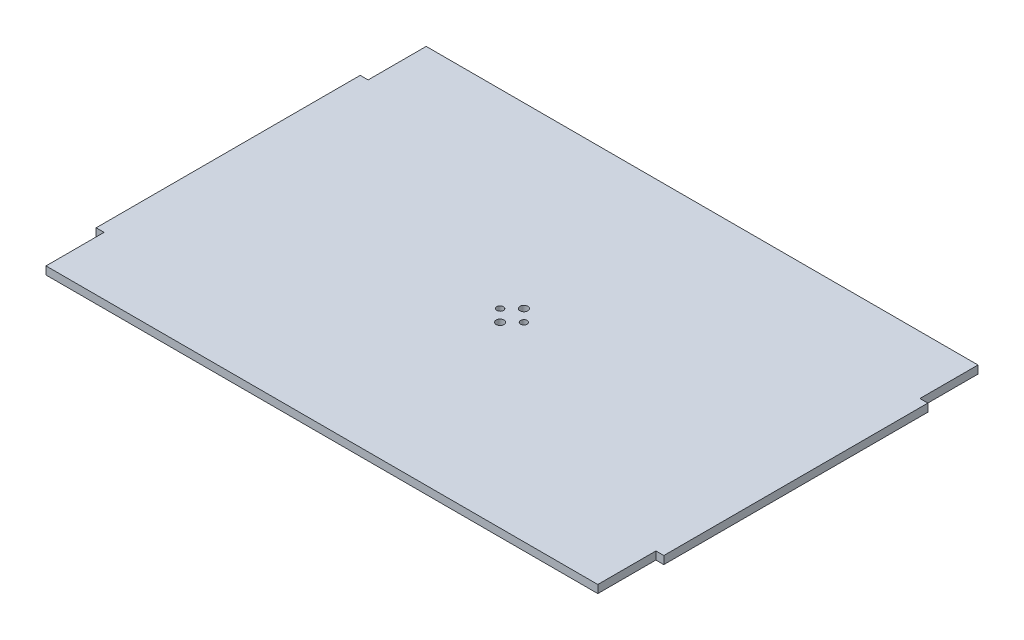
SolidWorks part; units mm, degrees
ref_plane "Front" through (0, 0, 0) normal (0, 0, 1) x (1, 0, 0)
ref_plane "Top" through (0, 0, 0) normal (0, 1, 0) x (1, 0, 0)
ref_plane "Right" through (0, 0, 0) normal (1, 0, 0) x (0, 0, -1)
sketch "Sketch1" plane through (0, 0, 0) normal (0, 1, 0) x (1, 0, 0)
  line L0 (418, 244) -> (424, 244)
  line L1 (0, 0) -> (418, 0)
  line L3 (0, 288) -> (418, 288)
  line L5 (424, 244) -> (424, 44)
  line L6 (424, 44) -> (418, 44)
  line L7 (418, 0) -> (418, 44)
  line L8 (418, 244) -> (418, 288)
  line L9 (0, 288) -> (0, 244)
  line L11 (0, 244) -> (-6, 244)
  line L13 (-6, 244) -> (-6, 44)
  line L14 (-6, 44) -> (0, 44)
  line L15 (0, 44) -> (0, 0)
  point P7 (424, 144)
  point P11 (-6, 144)
  dimension "D1" = 288
  dimension "D3" = 200
  dimension "D5" = 6
  dimension "D6" = 6
  dimension "D8" = 44
  dimension "D10" = 418
extrude "Boss-Extrude1" add sketch "Sketch1" along normal blind 6
sketch "Sketch2" plane through (0, 6, 0) normal (0, 1, 0) x (1, 0, 0)
  line L0 (418, 288) -> (0, 288) construction
  line L1 (209, 153) -> (209, 135) construction
  line L2 (200, 144) -> (218, 144) construction
  line L5 (424, 44) -> (424, 244) construction
  circle A1 centre (209, 135) radius 3
  circle A2 centre (209, 153) radius 3
  circle A3 centre (200, 144) radius 2.5
  circle A4 centre (218, 144) radius 2.5
  point P0 (209, 144)
  dimension "D1" = 9
  dimension "D4" = 6
  dimension "D5" = 5
  dimension "D7" = 18
  dimension "D8" = 144
  dimension "D3" = 9
  dimension "D2" = 215
  dimension "D6" = 18
extrude "Cut-Extrude1" cut sketch "Sketch2" against normal blind 6
